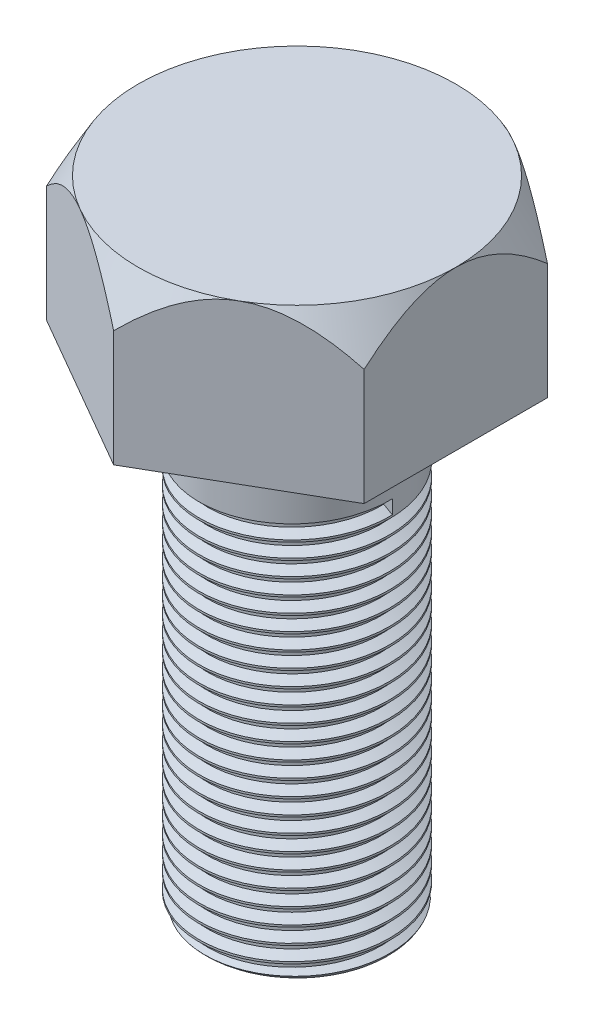
SolidWorks part; units mm, degrees
ref_plane "Front Plane" through (0, 0, 0) normal (0, 0, 1) x (1, 0, 0)
ref_plane "Top Plane" through (0, 0, 0) normal (0, 1, 0) x (1, 0, 0)
ref_plane "Right Plane" through (0, 0, 0) normal (1, 0, 0) x (0, 0, -1)
sketch "Sketch1" plane through (0, 0, 0) normal (0, 1, 0) x (1, 0, 0)
  line L1 (0, 23.094) -> (-20, 11.547)
  line L2 (-20, 11.547) -> (-20, -11.547)
  line L3 (-20, -11.547) -> (0, -23.094)
  line L4 (0, -23.094) -> (20, -11.547)
  line L5 (20, -11.547) -> (20, 11.547)
  line L6 (20, 11.547) -> (0, 23.094)
  circle A0 centre (0, 0) radius 20 construction
  dimension "D1" = 20
extrude "Boss-Extrude1" add sketch "Sketch1" along normal blind 20
sketch "Sketch2" plane through (0, 20, 0) normal (0, 1, 0) x (1, 0, 0)
  circle A0 centre (0, 0) radius 20
  dimension "D1" = 40
sketch "Sketch5" plane through (0, 0, 0) normal (0, -1, 0) x (1, 0, 0)
  circle A0 centre (0, 0) radius 12
  dimension "D1" = 24
extrude "Cut-Extrude3" cut sketch "Sketch2" against normal through all draft 30 flip side to cut
extrude "Boss-Extrude4" add sketch "Sketch5" along normal blind 60
fillet "Fillet1" radius 2 1 edges at (0, -60, -12)
thread "Thread1" pitch 2 profile "Thread Profile1" start angle 0, offset 3, length 0, pitch 2, diameter 24
ref_plane "Plane1" through (12, -61, 0) normal (0, 0, 1) x (1, 0, 0)
sketch "Thread Profile1" plane through (12, -61, 0) normal (0, 0, 1) x (1, 0, 0)
  line L0 (0, 0) -> (0, 2) construction
  line L11 (0, 0) -> (0, 1.75)
  line L12 (0, 1.75) -> (-1.0825, 1.125)
  line L13 (-1.0825, 1.125) -> (-1.0825, 0.625)
  line L15 (-1.0825, 0.625) -> (0, 0)
  line L17 (-1.0825, 0.875) -> (0, 0.875) construction
  point P2 (0, 0)
  dimension "Pitch" = 2
  dimension "Profile_Angle" = 60
  dimension "Profile_Land" = 0.5
  dimension "Profile_Height" = 1.0825
